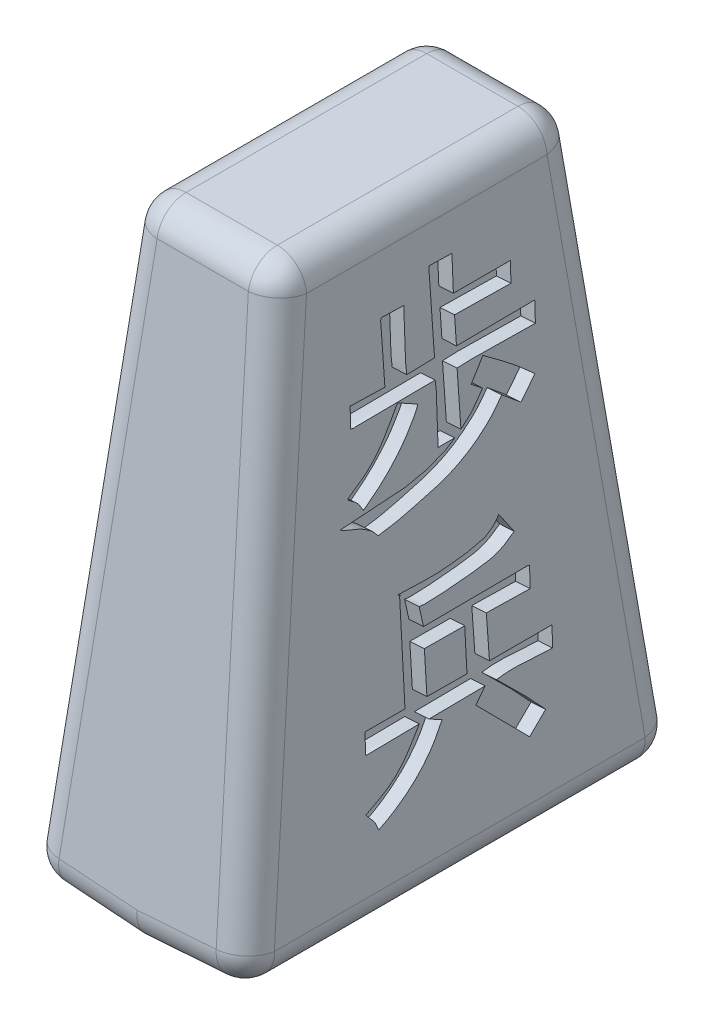
SolidWorks part; units mm, degrees
ref_plane "Płaszczyzna przednia" through (0, 0, 0) normal (0, 0, 1) x (1, 0, 0)
ref_plane "Płaszczyzna górna" through (0, 0, 0) normal (0, 1, 0) x (1, 0, 0)
ref_plane "Płaszczyzna prawa" through (0, 0, 0) normal (1, 0, 0) x (0, 0, -1)
sketch "Szkic1" plane through (0, 0, 0) normal (0, 0, 1) x (1, 0, 0)
  line L0 (0, 0) -> (0, 40)
  line L1 (3.1225, 40) -> (-3.1225, 40)
  line L2 (-5.1185, 38.1262) -> (-7.3738, 2.4704)
  line L3 (-5.504, 0.3481) -> (0, 0)
  line L4 (5.504, 0.3481) -> (0, 0)
  line L5 (5.1185, 38.1262) -> (7.3738, 2.4704)
  arc A0 (-3.1225, 40) -> (-5.1185, 38.1262) centre (-3.1225, 38) ccw
  arc A1 (-7.3738, 2.4704) -> (-5.504, 0.3481) centre (-5.3777, 2.3441) ccw
  arc A2 (7.3738, 2.4704) -> (5.504, 0.3481) centre (5.3777, 2.3441) cw
  arc A3 (3.1225, 40) -> (5.1185, 38.1262) centre (3.1225, 38) cw
  point P7 (-5, 40)
  point P10 (-7.5, 0.4744)
  point P17 (7.5, 0.4744)
  point P18 (5, 40)
  dimension "D5" = 2
  dimension "D1" = 40
  dimension "D2" = 90
  dimension "D3" = 5
  dimension "D4" = 7.5
extrude "Dodanie-wyciągnięcie1" add sketch "Szkic1" along normal blind 30 contours L2 A1 L3 L0 L1 A0 | A3 L1 L0 L4 A2 L5 region at (-3.1441, 18.7866, 0) region at (3.1441, 18.7866, 0)
ref_plane "Płaszczyzna1" through (5.1225, 0, 0) normal (1, 0, 0) x (0, 0, -1)
ref_plane "Płaszczyzna2" through (15.1225, 0, 0) normal (1, 0, 0) x (0, 0, -1)
sketch "Szkic7" plane through (15.1225, 0, 0) normal (1, 0, 0) x (0, 0, -1)
  line L0 (-25, 40) -> (-5, 40)
  line L1 (-30, 40) -> (0, 40) construction
  line L2 (-5, 40) -> (0, 0)
  line L3 (0, 0) -> (-30, 0)
  line L4 (-30, 0) -> (0, 0) construction
  line L5 (-15, 0) -> (-15, 40)
  line L6 (-25, 40) -> (-30, 0)
  line L8 (0, 0) -> (-30, 0)
  line L9 (0, 0) -> (0, 40)
  line L10 (0, 40) -> (-30, 40)
  line L11 (-30, 0) -> (-30, 40)
  dimension "D1" = 10
  dimension "D2" = 15
  dimension "D3" = 40
extrude "Wytnij-wyciągnięcie11" cut sketch "Szkic7" against normal through all and the other way through all contours L11 L6 L10 | L9 L10 L2 region at (15.1225, 26.6667, 28.3333) region at (15.1225, 26.6667, 1.6667)
fillet "Zaokrąglenie2" radius 2 18 edges at (0, 40, 5) (-4.4914, 39.4582, 4.9323) (-6.2461, 20.2983, 2.5373) (-6.8784, 1.022, 0.1278) (-2.752, 0.1741, 0.0218) (2.752, 0.1741, 0.0218) (6.8784, 1.022, 0.1278) (6.2461, 20.2983, 2.5373) (4.4914, 39.4582, 4.9323) (4.4914, 39.4582, 25.0677) (6.2461, 20.2983, 27.4627) (6.8784, 1.022, 29.8722) (2.752, 0.1741, 29.9782) (-2.752, 0.1741, 29.9782) (-6.8784, 1.022, 29.8722) (-6.2461, 20.2983, 27.4627) (-4.4914, 39.4582, 25.0677) (0, 40, 25)
sketch "Szkic10" plane through (7.5, 0.4744, 0) normal (0.998, 0.0631, 0) x (0, 0, -1)
  line L0 (341.3333, 1024) -> (1706.6667, 1024) construction
  line L1 (-15.0151, 35.3246) -> (-13.4351, 35.2846)
  line L2 (-13.4351, 35.2846) -> (-13.4751, 33.0046)
  line L3 (-13.4751, 33.0046) -> (-9.5751, 33.0046)
  line L4 (-9.5751, 33.0046) -> (-9.6151, 31.7046)
  line L5 (-9.6151, 31.7046) -> (-13.4751, 31.7646)
  line L6 (-13.4751, 31.7646) -> (-13.4551, 29.9646)
  line L7 (-8.0951, 29.9846) -> (-8.1351, 28.6846)
  line L8 (-13.4951, 28.7046) -> (-13.4551, 25.1646)
  line L9 (-11.8751, 26.7646) -> (-12.6151, 27.3446)
  line L10 (-12.6151, 27.3446) -> (-11.7351, 28.5846)
  line L11 (-8.3351, 25.8846) -> (-9.3751, 24.7446)
  line L12 (-9.3751, 24.7446) -> (-10.6151, 25.7646)
  line L13 (-13.8951, 24.8846) -> (-15.0351, 24.8846)
  line L14 (-20.7751, 28.7246) -> (-20.7351, 30.0246)
  line L15 (-20.7351, 30.0246) -> (-18.3551, 29.9646)
  line L16 (-18.3751, 33.9646) -> (-16.8151, 33.9246)
  line L17 (-16.8551, 29.9646) -> (-14.9551, 30.0046)
  line L18 (-14.9551, 30.0046) -> (-15.0151, 35.3246)
  line L19 (-11.2351, 19.1846) -> (-10.2751, 17.7446)
  line L20 (-16.8551, 16.6046) -> (-16.6351, 15.3446)
  line L21 (-9.3751, 15.3646) -> (-9.4151, 14.0246)
  line L22 (-9.4151, 14.0246) -> (-12.4151, 14.0846)
  line L23 (-12.4151, 14.0846) -> (-12.3751, 11.3046)
  line L24 (-12.3751, 11.3046) -> (-8.0951, 11.3046)
  line L25 (-8.0951, 11.3046) -> (-8.1351, 9.9846)
  line L26 (-8.8151, 6.7846) -> (-9.9751, 5.7646)
  line L27 (-9.9751, 5.7646) -> (-13.4351, 9.2646)
  line L28 (-13.4351, 9.2646) -> (-12.7551, 10.0446)
  line L29 (-12.7551, 10.0446) -> (-16.5951, 10.0046)
  line L30 (-16.5951, 10.0046) -> (-15.7351, 9.5446)
  line L31 (-20.9351, 10.0246) -> (-20.8951, 11.3446)
  line L32 (-20.8951, 11.3446) -> (-18.1551, 11.3446)
  line L33 (-18.1551, 11.3446) -> (-18.1151, 17.8246)
  line L34 (-18.1151, 17.8246) -> (-18.0351, 17.7846)
  line L35 (-18.0351, 17.7846) -> (-18.2151, 17.9446)
  line L36 (-16.6551, 14.0846) -> (-13.8951, 14.0646)
  line L37 (-13.8951, 14.0646) -> (-13.9151, 11.3046)
  line L38 (-13.9151, 11.3046) -> (-16.6551, 11.3246)
  line L39 (-16.6551, 11.3246) -> (-16.6551, 14.0846)
  spline S0 degree 3 poles (-13.4551, 29.9646) (-11.7218, 29.9779) (-9.9884, 29.9848) (-8.2551, 30.0046) (-8.2402, 30.0048) (-8.2299, 30.0265) (-8.2151, 30.0246) (-8.1733, 30.0194) (-8.1351, 29.9979) (-8.0951, 29.9846) knots 0 0 0 0 1 1 1 2 2 2 3 3 3 3
  spline S1 degree 3 poles (-8.1351, 28.6846) (-9.5818, 28.7046) (-11.0283, 28.7392) (-12.4751, 28.7446) (-12.8154, 28.7459) (-13.1551, 28.7179) (-13.4951, 28.7046) knots 0 0 0 0 1 1 1 2 2 2 2
  spline S2 degree 3 poles (-13.4551, 25.1646) (-13.2018, 25.3713) (-12.9248, 25.552) (-12.6951, 25.7846) (-12.3958, 26.0877) (-12.1484, 26.4379) (-11.8751, 26.7646) knots 0 0 0 0 1 1 1 2 2 2 2
  spline S3 degree 3 poles (-11.7351, 28.5846) (-11.0751, 28.0913) (-10.4004, 27.617) (-9.7551, 27.1046) (-9.2664, 26.7165) (-8.8084, 26.2913) (-8.3351, 25.8846) knots 0 0 0 0 1 1 1 2 2 2 2
  spline S4 degree 3 poles (-10.6151, 25.7646) (-10.8884, 25.4646) (-11.1373, 25.1403) (-11.4351, 24.8646) (-11.766, 24.5584) (-12.1226, 24.2786) (-12.4951, 24.0246) (-12.8579, 23.7773) (-13.2392, 23.5545) (-13.6351, 23.3646) (-14.0615, 23.1601) (-14.5013, 22.9776) (-14.9551, 22.8446) (-15.9373, 22.5568) (-16.9353, 22.3237) (-17.9351, 22.1046) (-18.3965, 22.0035) (-18.8684, 21.9579) (-19.3351, 21.8846) knots 0 0 0 0 1 1 1 2 2 2 3 3 3 4 4 4 5 5 5 6 6 6 6
  spline S5 degree 3 poles (-19.3351, 21.8846) (-19.4618, 22.0313) (-19.5656, 22.2013) (-19.7151, 22.3246) (-19.9491, 22.5175) (-20.205, 22.6868) (-20.4751, 22.8246) (-20.9165, 23.0497) (-21.4228, 23.1498) (-21.8351, 23.4246) knots 0 0 0 0 1 1 1 2 2 2 3 3 3 3
  spline S6 degree 3 poles (-21.8351, 23.4246) (-20.3484, 23.5179) (-18.8614, 23.6055) (-17.3751, 23.7046) (-17.3602, 23.7056) (-17.3497, 23.7217) (-17.3351, 23.7246) (-16.8759, 23.8152) (-16.4144, 23.8941) (-15.9551, 23.9846) (-15.9405, 23.9875) (-15.9292, 23.9996) (-15.9151, 24.0046) (-15.4957, 24.153) (-15.0729, 24.2916) (-14.6551, 24.4446) (-14.5991, 24.4651) (-14.5467, 24.4947) (-14.4951, 24.5246) (-14.2933, 24.6415) (-14.0951, 24.7646) (-13.8951, 24.8846) knots 0 0 0 0 1 1 1 2 2 2 3 3 3 4 4 4 5 5 5 6 6 6 7 7 7 7
  spline S7 degree 3 poles (-15.0351, 24.8846) (-15.0084, 25.9913) (-14.9666, 27.0977) (-14.9551, 28.2046) (-14.9532, 28.3851) (-14.9818, 28.5646) (-14.9951, 28.7446) knots 0 0 0 0 1 1 1 2 2 2 2
  spline S8 degree 3 poles (-14.9951, 28.7446) (-16.8284, 28.7313) (-18.6618, 28.7245) (-20.4951, 28.7046) (-20.51, 28.7044) (-20.5202, 28.6835) (-20.5351, 28.6846) (-20.616, 28.6904) (-20.6951, 28.7113) (-20.7751, 28.7246) knots 0 0 0 0 1 1 1 2 2 2 3 3 3 3
  spline S9 degree 3 poles (-18.3551, 29.9646) (-18.3684, 31.2046) (-18.3753, 32.4447) (-18.3951, 33.6846) (-18.3953, 33.6995) (-18.4162, 33.7097) (-18.4151, 33.7246) (-18.4093, 33.8055) (-18.3884, 33.8846) (-18.3751, 33.9646) knots 0 0 0 0 1 1 1 2 2 2 3 3 3 3
  spline S10 degree 3 poles (-16.8151, 33.9246) (-16.8418, 32.8446) (-16.8842, 31.7649) (-16.8951, 30.6846) (-16.8975, 30.4442) (-16.8684, 30.2046) (-16.8551, 29.9646) knots 0 0 0 0 1 1 1 2 2 2 2
  spline S11 degree 3 poles (-20.2551, 23.8446) (-20.3729, 24.0036) (-20.4397, 24.2003) (-20.5751, 24.3446) (-20.7504, 24.5313) (-20.9824, 24.6559) (-21.1751, 24.8246) (-21.1975, 24.8442) (-21.239, 24.8868) (-21.2151, 24.9046) (-20.8253, 25.1953) (-20.3832, 25.4116) (-19.9951, 25.7046) (-19.7013, 25.9264) (-19.4246, 26.1738) (-19.1751, 26.4446) (-18.5534, 27.1194) (-18.0752, 27.9153) (-17.5751, 28.6846) knots 7 7 7 7 8 8 8 9 9 9 10 10 10 11 11 11 12 12 12 13 13 13 13
  spline S12 degree 3 poles (-17.5751, 28.6846) (-17.1818, 28.4713) (-16.7843, 28.2654) (-16.3951, 28.0446) (-16.3371, 28.0117) (-16.21, 27.9864) (-16.2351, 27.9246) (-16.3906, 27.5423) (-16.6349, 27.2003) (-16.8751, 26.8646) (-17.1563, 26.4717) (-17.4636, 26.096) (-17.7951, 25.7446) (-18.1318, 25.3877) (-18.4948, 25.0546) (-18.8751, 24.7446) (-19.2896, 24.4067) (-19.7272, 24.0967) (-20.1751, 23.8046) (-20.2001, 23.7883) (-20.2374, 23.8206) (-20.2551, 23.8446) knots 0 0 0 0 1 1 1 2 2 2 3 3 3 4 4 4 5 5 5 6 6 6 7 7 7 7
  spline S13 degree 3 poles (-10.2751, 17.7446) (-10.5551, 17.5779) (-10.8179, 17.3782) (-11.1151, 17.2446) (-11.4151, 17.1098) (-11.731, 17.0006) (-12.0551, 16.9446) (-12.8553, 16.8065) (-13.6661, 16.7348) (-14.4751, 16.6646) (-15.1268, 16.6081) (-15.7811, 16.5811) (-16.4351, 16.5646) (-16.5757, 16.5611) (-16.7151, 16.5913) (-16.8551, 16.6046) knots 0 0 0 0 1 1 1 2 2 2 3 3 3 4 4 4 5 5 5 5
  spline S14 degree 3 poles (-16.6351, 15.3446) (-14.3018, 15.3579) (-11.9684, 15.3647) (-9.6351, 15.3846) (-9.6202, 15.3847) (-9.61, 15.4058) (-9.5951, 15.4046) (-9.5208, 15.3989) (-9.4484, 15.3779) (-9.3751, 15.3646) knots 0 0 0 0 1 1 1 2 2 2 3 3 3 3
  spline S15 degree 3 poles (-8.1351, 9.9846) (-9.415, 10.0053) (-10.7125, 10.235) (-11.9751, 10.0246) knots 0 0 0 0 1 1 1 1
  spline S16 degree 3 poles (-11.9751, 10.0246) (-11.3418, 9.3979) (-10.6972, 8.7824) (-10.0751, 8.1446) (-9.6436, 7.7022) (-9.2351, 7.2379) (-8.8151, 6.7846) knots 0 0 0 0 1 1 1 2 2 2 2
  spline S17 degree 3 poles (-15.7351, 9.5446) (-15.9551, 9.1913) (-16.148, 8.8195) (-16.3951, 8.4846) (-16.6561, 8.1308) (-16.9442, 7.7955) (-17.566, 7.1737) (-17.903, 6.8879) (-18.2551, 6.6246) (-18.6179, 6.3533) (-19.0027, 6.111) (-19.3951, 5.8846) (-19.6973, 5.7103) (-20.0218, 5.5779) (-20.3351, 5.4246) knots 0 0 0 0 1 1 1 2 2 3 3 3 4 4 4 5 5 5 5
  spline S18 degree 3 poles (-20.3351, 5.4246) (-20.4151, 5.6113) (-20.4661, 5.8133) (-20.5751, 5.9846) (-20.7328, 6.2323) (-20.9644, 6.4257) (-21.1351, 6.6646) knots 0 0 0 0 1 1 1 2 2 2 2
  spline S19 degree 3 poles (-21.1351, 6.6646) (-21.1084, 6.6779) (-21.0817, 6.6911) (-21.0551, 6.7046) (-20.6217, 6.9245) (-20.1718, 7.1146) (-19.7551, 7.3646) (-19.4361, 7.556) (-19.1288, 7.7727) (-18.8551, 8.0246) (-18.2231, 8.6063) (-17.7468, 9.3403) (-17.2551, 10.0446) knots 0 0 0 0 1 1 1 2 2 2 3 3 3 4 4 4 4
  spline S20 degree 3 poles (-17.2551, 10.0446) (-18.4218, 10.0313) (-19.5885, 10.0244) (-20.7551, 10.0046) (-20.77, 10.0044) (-20.7803, 9.983) (-20.7951, 9.9846) (-20.8433, 9.99) (-20.8884, 10.0113) (-20.9351, 10.0246) knots 0 0 0 0 1 1 1 2 2 2 3 3 3 3
  spline S21 degree 3 poles (-18.2151, 17.9446) (-17.3351, 17.9246) (-16.455, 17.8588) (-15.5751, 17.8846) (-14.859, 17.9056) (-14.1479, 18.0127) (-13.4351, 18.0846) (-13.4203, 18.0861) (-13.4097, 18.1014) (-13.3951, 18.1046) (-13.0159, 18.1882) (-12.6343, 18.261) (-12.2551, 18.3446) (-12.2405, 18.3478) (-12.2277, 18.3566) (-12.2151, 18.3646) (-12.0276, 18.4833) (-11.8253, 18.5822) (-11.6551, 18.7246) (-11.4959, 18.8578) (-11.3751, 19.0313) (-11.2351, 19.1846) knots 0 0 0 0 1 1 1 2 2 2 3 3 3 4 4 4 5 5 5 6 6 6 7 7 7 7
extrude "Wytnij-wyciągnięcie16" cut sketch "Szkic10" against normal blind 1 contours S10 L16 S9 L15 L14 S8 S7 L13 S6 S5 S4 L12 L11 S3 L10 L9 S2 L8 S1 L7 S0 L6 L5 L4 L3 L2 L1 L18 L17 | S21 L35 L34 L33 L32 L31 S20 S19 S18 S17 L30 L29 L28 L27 L26 S16 S15 L25 L24 L23 L22 L21 S14 L20 S13 L19 L38 L39 L36 L37 | S12 S11 region at (5.704, 28.869, 14.4239) region at (6.3411, 18.7972, 10.9128) region at (5.8437, 26.6615, 18.5479)
sketch "Szkic11" plane through (-7.5, 0.4744, 0) normal (-0.998, 0.0631, 0) x (0, 0, 1)
  line L0 (341.3333, 1024) -> (1706.6667, 1024) construction
  line L1 (14.0614, 20.3254) -> (19.6814, 23.5254)
  line L2 (19.6814, 23.5254) -> (18.9014, 24.3854)
  line L3 (18.9014, 24.3854) -> (20.0614, 25.4654)
  line L4 (8.9614, 27.5654) -> (9.0814, 29.1054)
  spline S0 degree 3 poles (9.0814, 29.1054) (9.6281, 29.1921) (10.1687, 29.3361) (10.7214, 29.3654) (11.2229, 29.392) (11.7742, 29.4538) (12.2214, 29.2254) (12.4977, 29.0843) (12.8116, 28.9937) (13.0414, 28.7854) (13.2525, 28.5942) (13.4068, 28.334) (13.5014, 28.0654) (13.618, 27.7346) (13.651, 27.376) (13.6614, 27.0254) (13.685, 26.2323) (13.5386, 25.4345) (13.6214, 24.6454) (13.7726, 23.2059) (13.9148, 21.7654) (14.0614, 20.3254) knots 0 0 0 0 1 1 1 2 2 2 3 3 3 4 4 4 5 5 5 6 6 6 7 7 7 7
  spline S1 degree 3 poles (20.0614, 25.4654) (20.6148, 25.1321) (21.2022, 24.8497) (21.7214, 24.4654) (22.0549, 24.2186) (22.3558, 23.9197) (22.6014, 23.5854) (22.7694, 23.3569) (22.8873, 23.0838) (22.9414, 22.8054) (22.9836, 22.5886) (22.9777, 22.3443) (22.8814, 22.1454) (22.7664, 21.9076) (22.559, 21.7153) (22.3414, 21.5654) (21.951, 21.2964) (21.5133, 21.1011) (21.0814, 20.9054) (19.5258, 20.2007) (17.9236, 19.5994) (16.3814, 18.8654) (15.288, 18.345) (14.2181, 17.7714) (13.1814, 17.1454) (12.4815, 16.7228) (11.8095, 16.2488) (11.1814, 15.7254) (10.7648, 15.3782) (10.3868, 14.9793) (10.0614, 14.5454) (9.8414, 14.252) (9.6704, 13.9156) (9.5614, 13.5654) (9.4742, 13.285) (9.3984, 12.952) (9.5214, 12.6854) (9.6327, 12.4444) (9.6897, 12.1678) (9.8614, 11.9654) (10.0737, 11.7153) (10.346, 11.5079) (10.6414, 11.3654) (11.1029, 11.1429) (11.5985, 10.9828) (12.1014, 10.8854) (12.8784, 10.7349) (13.6704, 10.6513) (14.4614, 10.6254) (15.5079, 10.5912) (16.5549, 10.6727) (17.6014, 10.7054) (17.6225, 10.7061) (17.6406, 10.722) (17.6614, 10.7254) (18.5476, 10.8688) (19.4353, 11.0021) (20.3214, 11.1454) (20.9061, 11.24) (21.4707, 11.4632) (22.0614, 11.5054) (22.3457, 11.5257) (22.6411, 11.4614) (22.9014, 11.3454) (23.2662, 11.1828) (23.6168, 10.9656) (23.9014, 10.6854) (24.0587, 10.5306) (24.1441, 10.3029) (24.1814, 10.0854) (24.22, 9.8612) (24.219, 9.611) (24.1214, 9.4054) (24.0204, 9.1925) (23.8289, 9.0173) (23.6214, 8.9054) (23.3078, 8.7362) (22.9525, 8.6464) (22.6014, 8.5854) (21.5285, 8.399) (20.4478, 8.242) (19.3614, 8.1654) (17.9844, 8.0684) (16.6013, 8.0263) (15.2214, 8.0654) (14.2228, 8.0937) (13.2031, 8.1147) (12.2414, 8.3854) (11.575, 8.573) (10.8874, 8.6964) (10.2414, 8.9454) (9.7738, 9.1257) (9.3254, 9.3687) (8.9214, 9.6654) (8.5643, 9.9277) (8.2427, 10.2475) (7.9814, 10.6054) (7.7494, 10.9233) (7.5754, 11.2887) (7.4614, 11.6654) (7.3326, 12.0914) (7.2581, 12.5404) (7.2614, 12.9854) (7.2648, 13.438) (7.3393, 13.8957) (7.4814, 14.3254) (7.6359, 14.7925) (7.8657, 15.238) (8.1414, 15.6454) (8.4701, 16.1311) (8.8608, 16.5768) (9.2814, 16.9854) (10.1434, 17.8226) (11.1448, 18.5055) (12.1214, 19.2054) knots 0 0 0 0 1 1 1 2 2 2 3 3 3 4 4 4 5 5 5 6 6 6 7 7 7 8 8 8 9 9 9 10 10 10 11 11 11 12 12 12 13 13 13 14 14 14 15 15 15 16 16 16 17 17 17 18 18 18 19 19 19 20 20 20 21 21 21 22 22 22 23 23 23 24 24 24 25 25 25 26 26 26 27 27 27 28 28 28 29 29 29 30 30 30 31 31 31 32 32 32 33 33 33 34 34 34 35 35 35 36 36 36 37 37 37 38 38 38 38
  spline S2 degree 3 poles (12.1214, 19.2054) (11.8548, 20.2187) (11.5321, 21.219) (11.3214, 22.2454) (11.0582, 23.5284) (10.9285, 24.8355) (10.7014, 26.1254) (10.635, 26.5029) (10.5281, 26.8721) (10.4414, 27.2454) knots 0 0 0 0 1 1 1 2 2 2 3 3 3 3
  spline S3 degree 3 poles (10.4414, 27.2454) (10.3348, 27.2987) (10.238, 27.3802) (10.1214, 27.4054) (9.7399, 27.4879) (9.3481, 27.5121) (8.9614, 27.5654) knots 0 0 0 0 1 1 1 2 2 2 2
extrude "Wytnij-wyciągnięcie17" cut sketch "Szkic11" against normal blind 1 contours S3 S2 S1 L3 L2 L1 S0 L4 region at (-6.1309, 22.1197, 17.0063)
